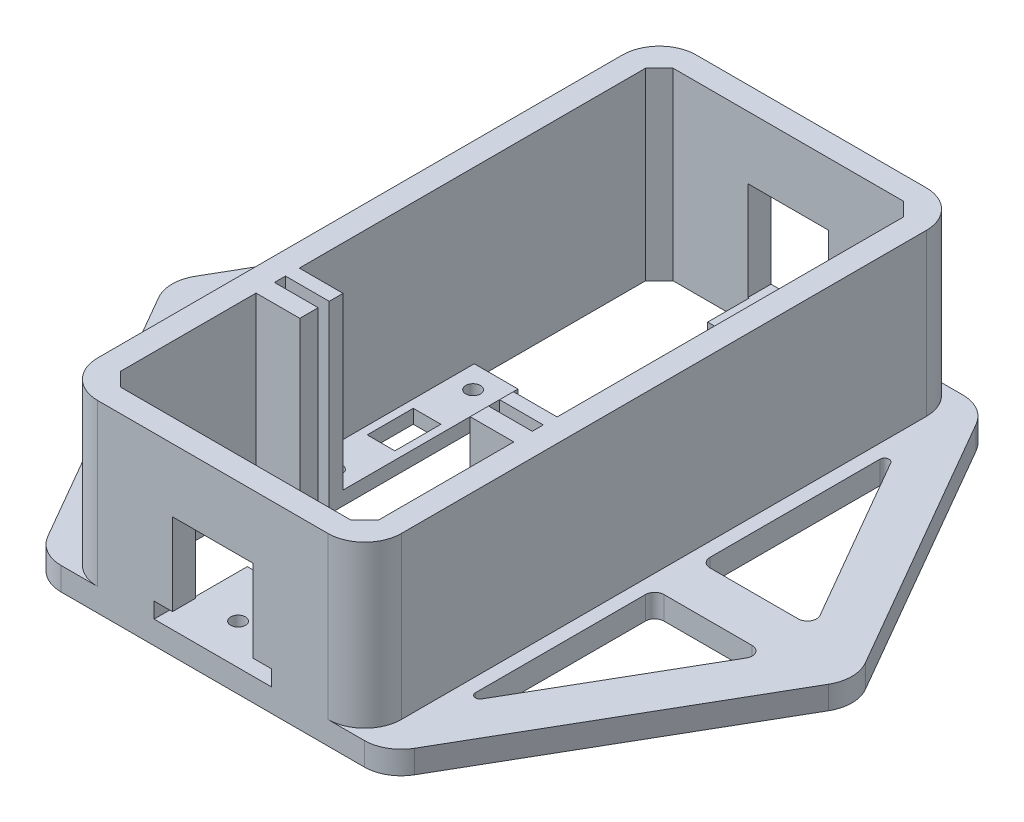
SolidWorks part; units mm, degrees
ref_plane "Front Plane" through (0, 0, 0) normal (0, 0, 1) x (1, 0, 0)
ref_plane "Top Plane" through (0, 0, 0) normal (0, 1, 0) x (1, 0, 0)
ref_plane "Right Plane" through (0, 0, 0) normal (1, 0, 0) x (0, 0, -1)
sketch "Sketch1" plane through (0, 0, 0) normal (0, 1, 0) x (1, 0, 0)
  line L1 (-75.0555, 0) -> (-37.5278, -65)
  line L2 (-37.5278, -65) -> (37.5278, -65)
  line L3 (37.5278, -65) -> (75.0555, 0)
  line L4 (75.0555, 0) -> (37.5278, 65)
  line L5 (37.5278, 65) -> (-37.5278, 65)
  line L6 (-37.5278, 65) -> (-75.0555, 0)
  circle A0 centre (0, 0) radius 65 construction
  circle A1 centre (0, 0) radius 50 construction
  dimension "D2" = 100
  dimension "D1" = 130
extrude "Boss-Extrude1" add sketch "Sketch1" along normal blind 5
fillet "Fillet1" radius 8 6 edges at (37.5278, 2.5, -65) (75.0555, 2.5, 0) (37.5278, 2.5, 65) (-37.5278, 2.5, 65) (-75.0555, 2.5, 0) (-37.5278, 2.5, -65)
sketch "Sketch3" plane through (0, 5, 0) normal (0, 1, 0) x (1, 0, 0)
  line L0 (-32.909, -65) -> (32.909, -65) construction
  line L1 (-25, 65) -> (25, 65)
  line L2 (-33, 57) -> (-33, -57)
  line L3 (-25, -65) -> (25, -65)
  line L4 (33, 57) -> (33, -57)
  line L5 (-33, 65) -> (33, -65) construction
  line L6 (-33, -65) -> (33, 65) construction
  arc A0 (33, 57) -> (25, 65) centre (25, 57) ccw
  arc A1 (33, -57) -> (25, -65) centre (25, -57) cw
  arc A2 (-25, -65) -> (-33, -57) centre (-25, -57) cw
  arc A3 (-25, 65) -> (-33, 57) centre (-25, 57) ccw
  point P0 (0, 0)
  dimension "D1" = 8
  dimension "D2" = 50
extrude "Boss-Extrude2" add sketch "Sketch3" along normal blind 35
sketch "Sketch4" plane through (0, 40, 0) normal (0, 1, 0) x (1, 0, 0)
  line L0 (-28, 57) -> (-25, 60)
  line L1 (25, 60) -> (28, 57)
  line L2 (28, -57) -> (25, -60)
  line L3 (-28, -57) -> (-25, -60)
  line L9 (-25, -60) -> (25, -60)
  line L10 (28, -57) -> (28, 57)
  line L11 (25, 60) -> (-25, 60)
  line L12 (-28, 57) -> (-28, -57)
  line L13 (-25, -60) -> (25, -60)
  line L14 (28, -57) -> (28, 57)
  line L15 (25, 60) -> (-25, 60)
  line L16 (-28, 57) -> (-28, -57)
  arc A9 (-28, -57) -> (-25, -60) centre (-25, -57) ccw
  arc A10 (25, -60) -> (28, -57) centre (25, -57) ccw
  arc A11 (28, 57) -> (25, 60) centre (25, 57) ccw
  arc A12 (-25, 60) -> (-28, 57) centre (-25, 57) ccw
  dimension "D1" = 5
extrude "Cut-Extrude1" cut sketch "Sketch4" against normal up to surface (40 mm away) up to face at (0, 0, 0)
sketch "Sketch8" plane through (0, 0, 0) normal (0, 1, 0) x (1, 0, 0)
  line L0 (0, 40) -> (0, 25) construction
  line L1 (0, 55) -> (0, 65) construction
  line L2 (9.5263, 26.5) -> (24.2487, 52) construction
  line L3 (22.5167, 55) -> (-22.5167, 55) construction
  line L4 (-24.2487, 52) -> (-9.5263, 26.5) construction
  line L5 (-12.5, 0) -> (-62.3346, 0) construction
  line L36 (6.9282, 25) -> (-6.9282, 25) construction
  line L37 (27.7128, 5) -> (57.1577, 5) construction
  line L38 (58.8897, 8) -> (36.3731, 47) construction
  line L39 (32.909, 47) -> (18.1865, 21.5) construction
  line L40 (25.1147, 6.5) -> (18.1865, 18.5) construction
  line L41 (18.1865, -21.5) -> (32.909, -47) construction
  line L42 (36.3731, -47) -> (58.8897, -8) construction
  line L43 (57.1577, -5) -> (27.7128, -5) construction
  line L44 (18.1865, -18.5) -> (25.1147, -6.5) construction
  line L45 (-9.5263, -26.5) -> (-24.2487, -52) construction
  line L46 (-22.5167, -55) -> (22.5167, -55) construction
  line L47 (24.2487, -52) -> (9.5263, -26.5) construction
  line L48 (-6.9282, -25) -> (6.9282, -25) construction
  line L49 (-27.7128, -5) -> (-57.1577, -5) construction
  line L50 (-58.8897, -8) -> (-36.3731, -47) construction
  line L51 (-32.909, -47) -> (-18.1865, -21.5) construction
  line L52 (-25.1147, -6.5) -> (-18.1865, -18.5) construction
  line L53 (-18.1865, 21.5) -> (-32.909, 47) construction
  line L54 (-37.866, 44.4141) -> (-58.8897, 8)
  line L55 (-57.1577, 5) -> (-38, 5)
  line L56 (-18.1865, 18.5) -> (-25.1147, 6.5) construction
  line L57 (-36, 7) -> (-36, 43.9141)
  line L58 (-33, 57) -> (-33, -57) construction
  line L59 (-36, -7) -> (-36, -43.9141)
  line L60 (-36.3731, 47) -> (-36, 47.6462) construction
  line L61 (-36, 5) -> (-27.7128, 5) construction
  line L71 (-33, 57) -> (-33, -57) construction
  line L72 (-57.1577, -5) -> (-38, -5)
  line L73 (-37.866, -44.4141) -> (-58.8897, -8)
  line L74 (37.866, -44.4141) -> (58.8897, -8)
  line L75 (57.1577, -5) -> (38, -5)
  line L76 (36, -7) -> (36, -43.9141)
  line L77 (36, 7) -> (36, 43.9141)
  line L78 (57.1577, 5) -> (38, 5)
  line L79 (37.866, 44.4141) -> (58.8897, 8)
  circle A0 centre (0, 0) radius 12.5 construction
  circle A1 centre (0, 40) radius 15 construction
  arc A3 (-22.5167, 55) -> (-24.2487, 52) centre (-22.5167, 53) ccw
  arc A4 (24.2487, 52) -> (22.5167, 55) centre (22.5167, 53) ccw construction
  arc A5 (6.9282, 25) -> (9.5263, 26.5) centre (6.9282, 28) ccw construction
  arc A6 (-6.9282, 25) -> (-9.5263, 26.5) centre (-6.9282, 28) cw construction
  arc A7 (25.1147, 6.5) -> (27.7128, 5) centre (27.7128, 8) ccw construction
  arc A8 (57.1577, 5) -> (58.8897, 8) centre (57.1577, 7) ccw construction
  arc A9 (36.3731, 47) -> (32.909, 47) centre (34.641, 46) ccw construction
  arc A10 (18.1865, 18.5) -> (18.1865, 21.5) centre (20.7846, 20) cw construction
  arc A11 (18.1865, -18.5) -> (18.1865, -21.5) centre (20.7846, -20) ccw construction
  arc A12 (32.909, -47) -> (36.3731, -47) centre (34.641, -46) ccw construction
  arc A13 (58.8897, -8) -> (57.1577, -5) centre (57.1577, -7) ccw construction
  arc A14 (25.1147, -6.5) -> (27.7128, -5) centre (27.7128, -8) cw construction
  arc A15 (-6.9282, -25) -> (-9.5263, -26.5) centre (-6.9282, -28) ccw construction
  arc A16 (-24.2487, -52) -> (-22.5167, -55) centre (-22.5167, -53) ccw construction
  arc A17 (22.5167, -55) -> (24.2487, -52) centre (22.5167, -53) ccw construction
  arc A18 (6.9282, -25) -> (9.5263, -26.5) centre (6.9282, -28) cw construction
  arc A19 (-25.1147, -6.5) -> (-27.7128, -5) centre (-27.7128, -8) ccw construction
  arc A20 (-57.1577, -5) -> (-58.8897, -8) centre (-57.1577, -7) ccw construction
  arc A21 (-36.3731, -47) -> (-32.909, -47) centre (-34.641, -46) ccw construction
  arc A22 (-18.1865, -18.5) -> (-18.1865, -21.5) centre (-20.7846, -20) cw construction
  arc A23 (-18.1865, 18.5) -> (-18.1865, 21.5) centre (-20.7846, 20) ccw construction
  arc A24 (-32.909, 47) -> (-36.3731, 47) centre (-34.641, 46) ccw construction
  arc A25 (-58.8897, 8) -> (-57.1577, 5) centre (-57.1577, 7) ccw
  arc A26 (-25.1147, 6.5) -> (-27.7128, 5) centre (-27.7128, 8) cw construction
  arc A28 (57.1577, -5) -> (58.8897, -8) centre (57.1577, -7) cw construction
  arc A31 (-36, 7) -> (-38, 5) centre (-38, 7) cw
  arc A32 (-36, 43.9141) -> (-37.866, 44.4141) centre (-37, 43.9141) ccw
  arc A33 (-36, -43.9141) -> (-37.866, -44.4141) centre (-37, -43.9141) cw
  arc A34 (-36, -7) -> (-38, -5) centre (-38, -7) ccw
  arc A35 (-58.8897, -8) -> (-57.1577, -5) centre (-57.1577, -7) cw
  arc A36 (57.1577, -5) -> (58.8897, -8) centre (57.1577, -7) cw construction
  arc A37 (58.8897, -8) -> (57.1577, -5) centre (57.1577, -7) ccw
  arc A38 (36, -7) -> (38, -5) centre (38, -7) cw
  arc A39 (36, -43.9141) -> (37.866, -44.4141) centre (37, -43.9141) ccw
  arc A40 (36, 43.9141) -> (37.866, 44.4141) centre (37, 43.9141) cw
  arc A41 (36, 7) -> (38, 5) centre (38, 7) ccw
  arc A42 (58.8897, 8) -> (57.1577, 5) centre (57.1577, 7) cw
  point P19 (0, 25)
  point P30 (0, 0)
  point P66 (0, 0)
  point P88 (0, 0)
  dimension "D1" = 25
  dimension "D3" = 30
  dimension "D6" = 2
  dimension "D8" = 3
  dimension "D11" = 2
  dimension "D12" = 1
  dimension "D2" = 40
  dimension "D4" = 10
  dimension "D5" = 15
  dimension "D7" = 25
  dimension "D9" = 3
extrude "Cut-Extrude2" cut sketch "Sketch8" along normal up to surface (5 mm away) contours A32 | L54 A25 L55 L57 | A35 L73 A33 L59 A34 L72 | L76 A39 L74 A37 L75 A38 | A42 L79 A40 L77 A41 L78 region at (-44.1761, 0, -19.1857) region at (-44.1761, 0, 19.1857) region at (44.1761, 0, 19.1857) region at (44.1761, 0, -19.1857) up to face at (-41.2442, 5, 0)
sketch "Sketch9" plane through (0, 0, 0) normal (0, -1, 0) x (1, 0, 0)
  line L0 (28, 57) -> (28, -57) construction
  line L1 (18.5, 20.1972) -> (28, 20.1972)
  line L2 (18.5, 20.1972) -> (18.5, -19.8028)
  line L3 (18.5, -19.8028) -> (28, -19.8028)
  line L4 (28, 20.1972) -> (28, -19.8028)
  line L5 (18.5, 20.1972) -> (28, -19.8028) construction
  line L6 (18.5, -19.8028) -> (28, 20.1972) construction
  line L7 (0, 0.1972) -> (23.25, 0.1972) construction
  line L8 (0, 0.1972) -> (0, -19.8028) construction
  line L9 (-18.5, -19.8028) -> (-28, -19.8028)
  line L10 (-28, 20.1972) -> (-28, -19.8028)
  line L11 (-18.5, 20.1972) -> (-28, 20.1972)
  line L12 (-18.5, 20.1972) -> (-18.5, -19.8028)
  point P4 (23.25, 0.1972)
  dimension "D1" = 23.25
  dimension "D2" = 40
  dimension "D3" = 9.5
extrude "Boss-Extrude3" add sketch "Sketch9" against normal blind 3
sketch "Sketch10" plane through (0, 3, 0) normal (0, 1, 0) x (1, 0, 0)
  line L0 (23.25, -0.1972) -> (23.25, -15.1972) construction
  line L1 (0, -0.1972) -> (23.25, -0.1972) construction
  line L2 (0, -0.1972) -> (0, 17.7568) construction
  line L3 (0, 0) -> (0, -0.1972) construction
  line L4 (-26.25, -5.1972) -> (-20.25, 4.8028) construction
  line L5 (26.25, 4.8028) -> (20.25, 4.8028)
  line L6 (26.25, 4.8028) -> (26.25, -5.1972)
  line L7 (26.25, -5.1972) -> (20.25, -5.1972)
  line L8 (20.25, 4.8028) -> (20.25, -5.1972)
  line L9 (26.25, 4.8028) -> (20.25, -5.1972) construction
  line L10 (26.25, -5.1972) -> (20.25, 4.8028) construction
  line L11 (-26.25, 4.8028) -> (-20.25, -5.1972) construction
  line L12 (-23.25, -0.1972) -> (-23.25, -15.1972) construction
  line L13 (-20.25, 4.8028) -> (-20.25, -5.1972)
  line L14 (-26.25, -5.1972) -> (-20.25, -5.1972)
  line L15 (-26.25, 4.8028) -> (-26.25, -5.1972)
  line L16 (-26.25, 4.8028) -> (-20.25, 4.8028)
  circle A1 centre (23.25, -15.1972) radius 1.6
  circle A2 centre (23.25, 14.8028) radius 1.6
  circle A3 centre (-23.25, 14.8028) radius 1.6
  circle A4 centre (-23.25, -15.1972) radius 1.6
  dimension "D1" = 23.25
  dimension "D3" = 3.2
  dimension "D2" = 15
  dimension "D4" = 6
  dimension "D5" = 10
extrude "Cut-Extrude3" cut sketch "Sketch10" against normal up to surface (3 mm away) up to face at (44.0289, 0, -18.855)
sketch "Sketch11" plane through (0, 0, 0) normal (0, -1, 0) x (1, 0, 0)
  line L0 (-28, -57) -> (-28, 57) construction
  line L5 (-28, 23.5972) -> (-18.5, 23.5972)
  line L6 (-18.5, 23.5972) -> (-18.5, 27.5972)
  line L7 (-28, 20.1972) -> (-28, 21.1972)
  line L8 (-18.5, 20.1972) -> (-28, 20.1972) construction
  line L9 (-28, 20.1972) -> (-18.5, 20.1972) construction
  line L10 (-18.5, -19.8028) -> (-18.5, 20.1972) construction
  line L11 (-28, 20.1972) -> (-28, 18.1972)
  line L12 (-28, 18.1972) -> (-18.5, 18.1972)
  line L13 (-18.5, 18.1972) -> (-18.5, 21.1972)
  line L14 (-18.5, 21.1972) -> (-28, 21.1972)
  line L15 (-28, 21.1972) -> (-28, 23.5972) construction
  line L16 (-18.5, 27.5972) -> (-28, 27.5972)
  line L17 (-28, 27.5972) -> (-28, 23.5972)
  line L18 (0, 0) -> (0, 78.4152) construction
  line L19 (28, 21.1972) -> (28, 23.5972) construction
  line L20 (28, 20.1972) -> (18.5, 20.1972) construction
  line L21 (28, 27.5972) -> (28, 23.5972)
  line L22 (18.5, 27.5972) -> (28, 27.5972)
  line L23 (18.5, 21.1972) -> (28, 21.1972)
  line L24 (18.5, 18.1972) -> (18.5, 21.1972)
  line L25 (28, 18.1972) -> (18.5, 18.1972)
  line L26 (28, 20.1972) -> (28, 18.1972)
  line L27 (28, 20.1972) -> (28, 21.1972)
  line L28 (18.5, 23.5972) -> (18.5, 27.5972)
  line L29 (28, 23.5972) -> (18.5, 23.5972)
  dimension "D1" = 4
  dimension "D3" = 1
  dimension "D4" = 2
  dimension "D5" = 2.4
extrude "Boss-Extrude4" add sketch "Sketch11" against normal up to surface (40 mm away) up to face at (0, 40, 0)
sketch "Sketch13" plane through (0, 0, 60) normal (0, 0, -1) x (-1, 0, 0)
  line L0 (0, 0) -> (0, 5) construction
  line L1 (-25, 0) -> (25, 0) construction
  line L2 (0, 0) -> (12.5, 5) construction
  line L3 (12.5, 5) -> (12.5, 0)
  line L4 (12.5, 0) -> (-12.5, 0)
  line L5 (12.5, 5) -> (-12.5, 5)
  line L6 (0, 0) -> (-12.5, 5) construction
  line L7 (-12.5, 5) -> (-12.5, 0)
  dimension "D1" = 12.5
extrude "Boss-Extrude5" add sketch "Sketch13" along normal up to surface (15 mm away)
sketch "Sketch15" plane through (0, 0, 0) normal (0, -1, 0) x (1, 0, 0)
  line L0 (12.5, 45) -> (12.5, 52.5) construction
  line L1 (12.5, 48.75) -> (-12.5, 48.75) construction
  line L2 (12.5, 48.75) -> (3.25, 48.75) construction
  line L3 (0, 45) -> (0, 60) construction
  line L4 (12.5, 45) -> (12.5, 48.75)
  line L5 (-12.5, 45) -> (-12.5, 52.5) construction
  line L6 (-12.5, 52.5) -> (12.5, 52.5) construction
  circle A0 centre (3.25, 48.75) radius 1.6
  circle A1 centre (-3.25, 48.75) radius 1.6
  circle A2 centre (-3.25, 56.25) radius 1.6
  circle A3 centre (3.25, 56.25) radius 1.6
  circle A4 centre (-3.25, 48.75) radius 3 construction
  dimension "D2" = 3.2
  dimension "D1" = 3.75
extrude "Cut-Extrude4" cut sketch "Sketch15" against normal blind 5 contours A0 | A3 | A1 | A2 region at (3.25, 0, 48.75) region at (-3.25, 0, 48.75) region at (-3.25, 0, 56.25) region at (3.25, 0, 56.25)
sketch "Sketch16" plane through (0, 0, 65) normal (0, 0, 1) x (1, 0, 0)
  line L0 (0, 0) -> (0, 5) construction
  line L1 (-32.909, 0) -> (32.909, 0) construction
  line L2 (-12.75, 5) -> (12.75, 5)
  line L3 (-12.75, 5) -> (-12.75, 8.4)
  line L4 (12.75, 5) -> (12.75, 7.5183)
  line L5 (-12.75, 8.4) -> (-8.75, 8.4)
  line L6 (-8.75, 8.4) -> (-8.75, 26.25)
  line L7 (-8.75, 26.25) -> (8.75, 26.25)
  line L8 (8.75, 8.4) -> (8.75, 26.25)
  line L9 (12.75, 8.4) -> (8.75, 8.4)
  line L10 (12.75, 5) -> (12.75, 8.4)
  point P7 (0, 5)
  point P13 (0, 26.25)
  dimension "D1" = 5
  dimension "D2" = 4
  dimension "D3" = 3.4
  dimension "D4" = 12.75
  dimension "D5" = 17.85
  dimension "D6" = 8.75
extrude "Cut-Extrude5" cut sketch "Sketch16" against normal up to surface (5 mm away) contours L2 L3 L5 L6 L7 L8 L9 L10 up to face at (0, 11.25, 60)
sketch "Sketch17" plane through (0, 0, -60) normal (0, 0, 1) x (1, 0, 0)
  line L0 (0, 0) -> (-8.5, 0) construction
  line L1 (-25, 0) -> (25, 0) construction
  line L3 (-8.5, 0) -> (8.5, 0)
  line L4 (-8.5, 0) -> (-8.5, 5)
  line L5 (-8.5, 5) -> (8.5, 5)
  line L6 (8.5, 0) -> (8.5, 5)
  line L7 (-8.5, 0) -> (8.5, 5) construction
  line L8 (-8.5, 5) -> (8.5, 0) construction
  point P7 (0, 2.5)
  dimension "D1" = 5
  dimension "D2" = 17
extrude "Boss-Extrude6" add sketch "Sketch17" along normal blind 9
sketch "Sketch18" plane through (0, 0, 0) normal (0, -1, 0) x (1, 0, 0)
  line L0 (0, -51) -> (0, -66) construction
  line L1 (8.5, -51) -> (-8.5, -51) construction
  line L2 (-8.5, -51) -> (8.5, -51) construction
  line L3 (3.25, -54.75) -> (3.25, -51) construction
  line L4 (3.25, -54.75) -> (8.5, -54.75) construction
  line L5 (-8.5, -51) -> (8.5, -51) construction
  line L6 (-8.5, -51) -> (8.5, -51) construction
  circle A0 centre (-3.25, -54.75) radius 1.6
  circle A1 centre (3.25, -54.75) radius 1.6
  circle A2 centre (3.25, -54.75) radius 3 construction
extrude "Cut-Extrude6" cut sketch "Sketch18" against normal blind 5
sketch "Sketch19" plane through (0, 0, -65) normal (0, 0, -1) x (-1, 0, 0)
  line L0 (0, 0) -> (0, 5) construction
  line L1 (-8.5, 5) -> (8.5, 5) construction
  line L9 (0, 5) -> (-8.75, 5)
  line L10 (-8.75, 5) -> (-8.75, 26.4)
  line L11 (-8.75, 26.4) -> (8.75, 26.4)
  line L12 (8.75, 5) -> (8.75, 26.4)
  line L13 (0, 5) -> (8.75, 5)
  point P8 (0, 26.4)
  point P9 (-8.5, 41.5554)
  point P10 (-8.75, 20.1554)
  point P11 (-7.1375, 17.325)
  point P12 (-9.5727, 5.0066)
  dimension "D1" = 8.75
  dimension "D2" = 21.4
extrude "Cut-Extrude8" cut sketch "Sketch19" against normal blind 5
